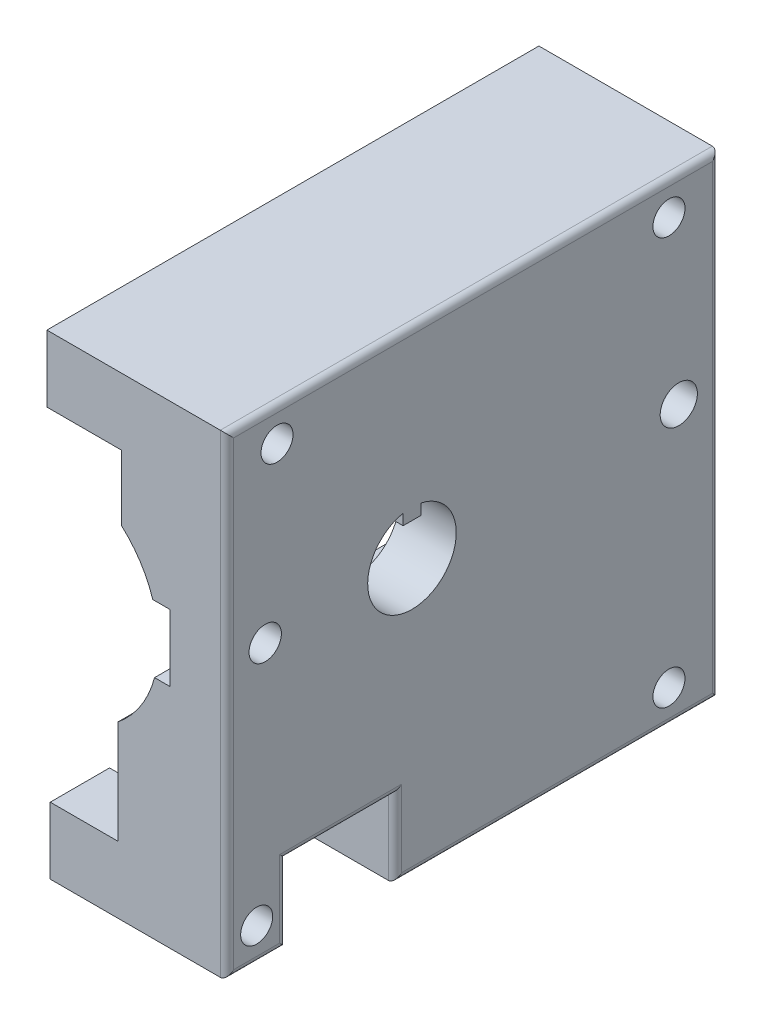
SolidWorks part; units mm, degrees
ref_plane "Front" through (0, 0, 0) normal (0, 0, 1) x (1, 0, 0)
ref_plane "Top" through (0, 0, 0) normal (0, 1, 0) x (1, 0, 0)
ref_plane "Right" through (0, 0, 0) normal (1, 0, 0) x (0, 0, -1)
sketch "Profile" plane through (0, 0, 0) normal (0, 0, 1) x (1, 0, 0)
  line L0 (-6.0107, -43.6279) -> (-6.0107, -33.6279)
  line L1 (-6.0107, -43.6279) -> (20.4893, -43.6279)
  line L2 (-6.5107, 17.4121) -> (-6.5107, 27.4121)
  line L3 (-6.5107, 27.4121) -> (20.4893, 27.4121)
  line L4 (20.4893, -43.6279) -> (20.4893, 27.4121)
  line L5 (-6.0107, -33.6279) -> (4.1393, -33.6279)
  line L6 (4.1393, -33.6279) -> (4.1393, -18.1379)
  line L7 (9.6313, -9.6379) -> (11.9493, -9.6379)
  line L8 (11.9493, -9.6379) -> (11.9493, 0.3621)
  line L9 (9.3593, 0.3621) -> (11.9493, 0.3621)
  line L10 (4.6393, 17.4121) -> (4.6393, 7.6371)
  line L11 (4.6393, 17.4121) -> (-6.5107, 17.4121)
  arc A0 (9.3593, 0.3621) -> (4.6393, 7.6371) centre (-6.1482, -4.5305) ccw
  arc A1 (4.1393, -18.1379) -> (9.6313, -9.6379) centre (-6.0948, -5.5013) ccw
  dimension "D14" = 16.261
  dimension "D17" = 16.261
  dimension "D2" = 10
  dimension "D3" = 2.59
  dimension "D4" = 2.318
  dimension "D5" = 9.775
  dimension "D6" = 11.15
  dimension "D7" = 15.49
  dimension "D8" = 10.15
  dimension "D9" = 10
  dimension "D10" = 26.5
  dimension "D11" = 71.04
  dimension "D12" = 27
  dimension "D13" = 10
  dimension "D15" = 23.99
  dimension "D16" = 5.492
extrude "ProfileExtrude" add sketch "Profile" along normal blind 73.76
sketch "HoseWindow" plane through (20.4893, 0, 0) normal (1, 0, 0) x (0, 0, -1)
  line L0 (-73.76, -43.6279) -> (0, -43.6279) construction
  line L1 (-64.87, -43.6279) -> (-48.58, -43.6279)
  line L2 (-64.87, -43.6279) -> (-64.87, -32.1279)
  line L3 (-64.87, -32.1279) -> (-48.58, -32.1279)
  line L4 (-48.58, -43.6279) -> (-48.58, -32.1279)
  line L5 (-73.76, -43.6279) -> (-73.76, 27.4121) construction
  dimension "D1" = 16.29
  dimension "D2" = 11.5
  dimension "D3" = 8.89
extrude "HoseWindowCut" cut sketch "HoseWindow" against normal through all
sketch "CageScrews" plane through (20.4893, 0, 0) normal (1, 0, 0) x (0, 0, -1)
  line L0 (-73.76, 27.4121) -> (0, 27.4121) construction
  line L1 (-73.76, -43.6279) -> (-73.76, 27.4121) construction
  line L2 (0, -43.6279) -> (0, 27.4121) construction
  line L3 (-48.58, -43.6279) -> (0, -43.6279) construction
  line L4 (-73.76, -43.6279) -> (-64.87, -43.6279) construction
  circle A0 centre (-66.26, 22.4121) radius 2.4
  circle A1 centre (-7.5, 22.4121) radius 2.4
  circle A2 centre (-7.5, -38.6279) radius 2.4
  circle A3 centre (-69.31, -38.6279) radius 2.4
  point P16 (0, 0)
  dimension "D1" = 4.8
  dimension "D2" = 4.8
  dimension "D3" = 4.8
  dimension "D4" = 4.8
  dimension "D5" = 5
  dimension "D6" = 7.5
  dimension "D7" = 7.5
  dimension "D8" = 5
  dimension "D9" = 5
  dimension "D10" = 7.5
  dimension "D11" = 5
  dimension "D12" = 4.45
extrude "CageScrewsCut" cut sketch "CageScrews" against normal through all
sketch "AxleHole" plane through (20.4893, 0, 0) normal (1, 0, 0) x (0, 0, -1)
  line L0 (-46.03, 2.3073) -> (-46.03, -9.2169) construction
  line L1 (-44.699, 2.3073) -> (-47.361, 2.3073)
  line L2 (-47.361, 2.3073) -> (-47.361, 3.9263)
  line L3 (-44.699, 2.3073) -> (-44.699, 3.9263)
  line L4 (-48.58, -43.6279) -> (0, -43.6279) construction
  line L5 (0, -43.6279) -> (0, 27.4121) construction
  arc A0 (-47.361, 3.9263) -> (-44.699, 3.9263) centre (-46.03, -2.5779) ccw
  dimension "D1" = 13.278
  dimension "D2" = 1.619
  dimension "D3" = 1.619
  dimension "D4" = 1.331
  dimension "D5" = 41.05
  dimension "D6" = 46.03
extrude "AxleHoleCut" cut sketch "AxleHole" against normal through all
sketch "SetScrews" plane through (20.4893, 0, 0) normal (1, 0, 0) x (0, 0, -1)
  line L0 (-46.03, -9.2169) -> (-46.03, -2.5779) construction
  circle A0 centre (-68.03, -2.5779) radius 2.4263
  circle A1 centre (-6.03, -2.5779) radius 2.7888
  arc A3 (-47.361, 3.9263) -> (-44.699, 3.9263) centre (-46.03, -2.5779) ccw construction
  dimension "D1" = 22
  dimension "D2" = 40
extrude "SetScrewsCut" cut sketch "SetScrews" against normal through all
fillet "Fillet1" radius 1 8 edges at (20.4893, -37.8779, 64.87) (20.4893, -37.8779, 48.58) (20.4893, -32.1279, 56.725) (20.4893, -43.6279, 69.315) (20.4893, -8.1079, 73.76) (20.4893, -43.6279, 24.29) (20.4893, -8.1079, 0) (20.4893, 27.4121, 36.88)
equation "\"BottomEdge\"=26.5mm"
equation "\"TopEdge\"=27mm"
equation "\"TotalHeight\"=71.04mm"
equation "\"TotalLength\"=73.76mm"
equation "\"Screw Clearance\" = 10mm"
equation "\"TopDepth\"= 11.15mm"
equation "\"BottomDepth\"=10.15mm"
equation "\"TopHeight\"=9.775mm"
equation "\"BottomHeight\"=15.49mm"
equation "\"TopChannelDepth\"=2.59mm"
equation "\"BottomChannelDepth\"=2.318mm"
equation "\"ChannelHeight\"=10mm"
equation "\"ChamberRadius\"=16.261mm"
equation "\"ChanRelHeight\"=23.99mm"
equation "\"ChanRelDepth\"=5.492mm"
equation "\"D2@Profile\"= \"ChannelHeight\""
equation "\"D4@Profile\"= \"BottomChannelDepth\""
equation "\"D3@Profile\"= \"TopChannelDepth\""
equation "\"D5@Profile\"= \"TopHeight\""
equation "\"D7@Profile\"= \"BottomHeight\""
equation "\"D9@Profile\"= \"Screw Clearance\""
equation "\"D13@Profile\"= \"Screw Clearance\""
equation "\"D8@Profile\"= \"BottomDepth\""
equation "\"D6@Profile\"= \"TopDepth\""
equation "\"D10@Profile\"= \"BottomEdge\""
equation "\"D12@Profile\"= \"TopEdge\""
equation "\"D11@Profile\"= \"TotalHeight\""
equation "\"D15@Profile\"= \"ChanRelHeight\""
equation "\"D16@Profile\"= \"ChanRelDepth\""
equation "\"D17@Profile\"= \"ChamberRadius\""
equation "\"D14@Profile\"= \"ChamberRadius\""
equation "\"D1@ProfileExtrude\"= \"TotalLength\""
equation "\"CageScrewDiameter\"=4.8mm"
equation "\"SetScrewDiameter\"=3.5mm"
equation "\"AxleRadius\"=6.639mm"
equation "\"KeyHeight\"=1.619mm"
equation "\"KeyWidth\"=2.662mm"
equation "\"HoseWindowWidth\"=16.29mm"
equation "\"HoseWindowHeight\"=11.5mm"
equation "\"HoseWindow-Edge\"=8.89mm"
equation "\"CageScrew-VerticalEdge\"=5.0mm"
equation "\"CageScrew-HorizontalEdge\"=7.5mm"
equation "\"CageScrew-HoseCornerScrewEdge\"=4.45mm"
equation "\"Axle-BottomEdge\"=41.05mm"
equation "\"Axle-FrontEdge\"=46.03mm"
equation "\"FrontSetScrew-Axel\"=40mm"
equation "\"D1@HoseWindow\"= \"HoseWindowWidth\""
equation "\"D2@HoseWindow\"= \"HoseWindowHeight\""
equation "\"D3@HoseWindow\"= \"HoseWindow-Edge\""
equation "\"D6@CageScrews\"= \"CageScrew-HorizontalEdge\""
equation "\"D7@CageScrews\"= \"CageScrew-HorizontalEdge\""
equation "\"D10@CageScrews\"= \"CageScrew-HorizontalEdge\""
equation "\"D12@CageScrews\"= \"CageScrew-HoseCornerScrewEdge\""
equation "\"D5@CageScrews\"= \"CageScrew-VerticalEdge\""
equation "\"D8@CageScrews\"= \"CageScrew-VerticalEdge\""
equation "\"D11@CageScrews\"= \"CageScrew-VerticalEdge\""
equation "\"D9@CageScrews\"= \"CageScrew-VerticalEdge\""
equation "\"D1@CageScrews\"= \"CageScrewDiameter\""
equation "\"D2@CageScrews\"= \"CageScrewDiameter\""
equation "\"D4@CageScrews\"= \"CageScrewDiameter\""
equation "\"D3@CageScrews\"= \"CageScrewDiameter\""
equation "\"D1@AxleHole\"= \"AxleRadius\" * 2"
equation "\"D3@AxleHole\"= \"KeyHeight\""
equation "\"D2@AxleHole\"= \"KeyHeight\""
equation "\"D4@AxleHole\"= \"KeyWidth\" / 2"
equation "\"D6@AxleHole\"= \"Axle-FrontEdge\""
equation "\"D5@AxleHole\"= \"Axle-BottomEdge\""
equation "\"D2@SetScrews\"= \"FrontSetScrew-Axel\""
equation "\"BackSetScrew-Axel\"=22mm"
equation "\"D1@SetScrews\"= \"BackSetScrew-Axel\""
